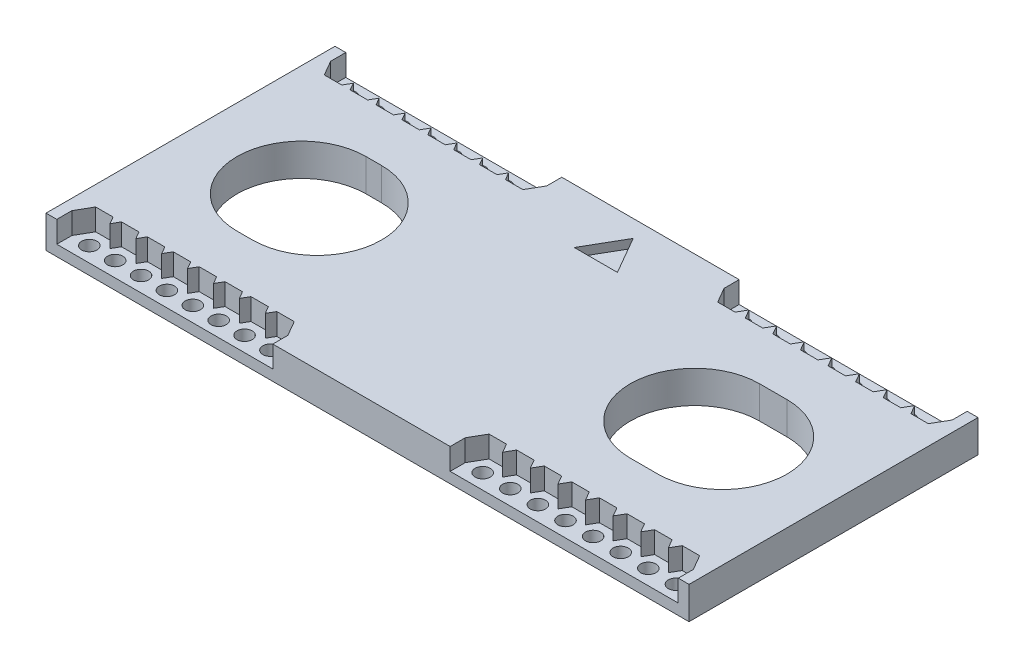
SolidWorks part; units mm, degrees
note: The reader was unsure of these and kept them because the rebuilt part matched: shared geometry of "Sketch1<5>".
ref_plane "Front Plane" through (0, 0, 0) normal (0, 0, 1) x (1, 0, 0)
ref_plane "Top Plane" through (0, 0, 0) normal (0, 1, 0) x (1, 0, 0)
ref_plane "Right Plane" through (0, 0, 0) normal (1, 0, 0) x (0, 0, -1)
sketch "Sketch1" plane through (0, 0, 0) normal (0, 1, 0) x (1, 0, 0)
  line L0 (0, 38.1) -> (0, -38.1) construction
  line L1 (156.464, 38.1) -> (164.592, -38.1) construction
  line L2 (-5.0555, 33.6582) -> (-3.81, 35.8155)
  line L3 (-5.0555, 33.6582) -> (178.2835, 33.6582)
  line L4 (-5.0555, 33.6582) -> (-5.0555, 0)
  line L5 (-5.0555, 0) -> (178.2835, 0)
  line L6 (178.2835, 33.6582) -> (178.2835, 0)
  line L7 (-3.81, 35.8155) -> (-2.5645, 33.6582)
  line L8 (0, 38.1) -> (-3.8467, 35.8791) construction
  line L9 (0, 38.1) -> (3.81, 38.1) construction
  line L10 (3.81, 38.1) -> (7.62, 38.1) construction
  line L11 (7.62, 38.1) -> (7.62, 33.6582) construction
  line L12 (0, 38.1) -> (-3.81, 38.1) construction
  line L13 (2.5645, 33.6582) -> (3.81, 35.8155)
  line L14 (3.81, 35.8155) -> (5.0555, 33.6582)
  line L15 (10.1845, 33.6582) -> (11.43, 35.8155)
  line L16 (11.43, 35.8155) -> (12.6755, 33.6582)
  line L17 (17.8045, 33.6582) -> (19.05, 35.8155)
  line L18 (19.05, 35.8155) -> (20.2955, 33.6582)
  line L19 (25.4245, 33.6582) -> (26.67, 35.8155)
  line L20 (26.67, 35.8155) -> (27.9155, 33.6582)
  line L21 (33.0445, 33.6582) -> (34.29, 35.8155)
  line L22 (34.29, 35.8155) -> (35.5355, 33.6582)
  line L23 (40.6645, 33.6582) -> (41.91, 35.8155)
  line L24 (41.91, 35.8155) -> (43.1555, 33.6582)
  line L25 (48.2845, 33.6582) -> (49.53, 35.8155)
  line L26 (49.53, 35.8155) -> (50.7755, 33.6582)
  line L27 (55.9045, 33.6582) -> (57.15, 35.8155)
  line L28 (57.15, 35.8155) -> (58.3955, 33.6582)
  line L29 (-3.81, 35.8155) -> (3.81, 35.8155) construction
  line L30 (7.62, 38.1) -> (15.24, 38.1) construction
  line L31 (178.2835, 33.6582) -> (176.784, 36.2554)
  line L32 (176.784, 36.2554) -> (175.2845, 33.6582)
  line L33 (172.72, 38.1) -> (176.5667, 35.8791) construction
  line L34 (172.72, 38.1) -> (176.784, 38.1) construction
  line L35 (172.72, 38.1) -> (168.656, 38.1) construction
  line L36 (168.656, 38.1) -> (164.592, 38.1) construction
  line L37 (170.1555, 33.6582) -> (168.656, 36.2554)
  line L38 (168.656, 36.2554) -> (167.1565, 33.6582)
  line L39 (162.0275, 33.6582) -> (160.528, 36.2554)
  line L40 (160.528, 36.2554) -> (159.0285, 33.6582)
  line L41 (153.8995, 33.6582) -> (152.4, 36.2554)
  line L42 (152.4, 36.2554) -> (150.9005, 33.6582)
  line L43 (145.7715, 33.6582) -> (144.272, 36.2554)
  line L44 (144.272, 36.2554) -> (142.7725, 33.6582)
  line L45 (137.6435, 33.6582) -> (136.144, 36.2554)
  line L46 (136.144, 36.2554) -> (134.6445, 33.6582)
  line L47 (129.5155, 33.6582) -> (128.016, 36.2554)
  line L48 (128.016, 36.2554) -> (126.5165, 33.6582)
  line L49 (121.3875, 33.6582) -> (119.888, 36.2554)
  line L50 (119.888, 36.2554) -> (118.3885, 33.6582)
  line L51 (113.2595, 33.6582) -> (111.76, 36.2554)
  line L52 (111.76, 36.2554) -> (110.2605, 33.6582)
  line L53 (-8.304, 42.5418) -> (181.024, 42.5418)
  line L54 (15.24, 42.5418) -> (15.24, 33.6582) construction
  line L55 (-5.129, 42.5418) -> (-5.129, 38.1)
  line L56 (-8.304, 42.5418) -> (-8.304, 0)
  line L58 (176.784, 36.2554) -> (177.849, 38.1)
  line L59 (177.849, 38.1) -> (177.849, 42.5418)
  line L60 (178.2835, 0) -> (181.024, 0)
  line L61 (-5.0555, 0) -> (-8.304, 0)
  line L62 (57.15, 35.8155) -> (58.469, 38.1)
  line L63 (58.469, 38.1) -> (58.469, 42.5418)
  line L64 (111.76, 36.2554) -> (110.695, 38.1)
  line L65 (110.695, 38.1) -> (110.695, 42.5418)
  line L66 (181.024, 42.5418) -> (181.024, 0)
  line L67 (-5.129, 38.1) -> (-3.8467, 35.8791)
  line L68 (-3.8467, 35.8791) -> (-3.81, 35.8155)
  circle A0 centre (0, 38.1) radius 2.2479
  circle A1 centre (0, -38.1) radius 2.2479 construction
  circle A2 centre (7.62, 38.1) radius 2.2479
  circle A3 centre (7.62, -38.1) radius 2.2479 construction
  circle A4 centre (15.24, 38.1) radius 2.2479
  circle A5 centre (15.24, -38.1) radius 2.2479 construction
  circle A6 centre (22.86, 38.1) radius 2.2479
  circle A7 centre (22.86, -38.1) radius 2.2479 construction
  circle A8 centre (30.48, 38.1) radius 2.2479
  circle A9 centre (30.48, -38.1) radius 2.2479 construction
  circle A10 centre (38.1, 38.1) radius 2.2479
  circle A11 centre (38.1, -38.1) radius 2.2479 construction
  circle A12 centre (45.72, 38.1) radius 2.2479
  circle A13 centre (45.72, -38.1) radius 2.2479 construction
  circle A14 centre (53.34, 38.1) radius 2.2479
  circle A15 centre (53.34, -38.1) radius 2.2479 construction
  circle A16 centre (115.824, 38.1) radius 2.2479
  circle A17 centre (115.824, -38.1) radius 2.2479 construction
  circle A18 centre (123.952, 38.1) radius 2.2479
  circle A19 centre (123.952, -38.1) radius 2.2479 construction
  circle A20 centre (132.08, 38.1) radius 2.2479
  circle A21 centre (132.08, -38.1) radius 2.2479 construction
  circle A22 centre (140.208, 38.1) radius 2.2479
  circle A23 centre (140.208, -38.1) radius 2.2479 construction
  circle A24 centre (148.336, 38.1) radius 2.2479
  circle A25 centre (148.336, -38.1) radius 2.2479 construction
  circle A26 centre (156.464, 38.1) radius 2.2479
  circle A27 centre (156.464, -38.1) radius 2.2479 construction
  circle A28 centre (164.592, 38.1) radius 2.2479
  circle A29 centre (164.592, -38.1) radius 2.2479 construction
  circle A30 centre (172.72, 38.1) radius 2.2479
  circle A31 centre (172.72, -38.1) radius 2.2479 construction
  circle A32 centre (15.24, 0) radius 19
  circle A34 centre (15.24, 0) radius 23.544
  point P4 (0, 0)
  point P79 (3.81, 38.1)
  dimension "D1" = 76.2
  dimension "D2" = 4.4958
  dimension "D5" = 8
  dimension "D8" = 38
  dimension "D15" = 3.175
  dimension "D4" = 7.62
  dimension "D6" = 8.128
  dimension "D7" = 117.348
  dimension "D9" = 4.4418
  dimension "D10" = 120
  dimension "D11" = 9
  dimension "D12" = 120
  dimension "D13" = 9
  dimension "D16" = 3.175
  dimension "D3" = 8
extrude "Boss-Extrude1" add sketch "Sketch1" against normal blind 9.525
extrude "Cut-Extrude1" cut sketch "Sketch1<5>" against normal blind 6.35
sketch "Sketch1<5>" plane through (0, 0, 0) normal (0, 1, 0) x (1, 0, 0) same geometry as "Sketch1"
mirror "Mirror1" about plane through (0, 0, 0) normal (0, 0, 1) of bodies 102
sketch "Sketch2" plane through (0, 0, 0) normal (0, 1, 0) x (1, 0, 0)
  line L0 (148.336, 0) -> (140.208, 0) construction
  line L1 (24.384, 0) -> (28.956, 0) construction
  line L3 (148.336, 0) -> (140.208, 0) construction
  line L4 (148.336, -19) -> (140.208, -19)
  line L5 (148.336, 19) -> (140.208, 19)
  line L6 (28.956, 0) -> (24.384, 0) construction
  line L7 (28.956, -19) -> (24.384, -19)
  line L8 (28.956, 19) -> (24.384, 19)
  arc A2 (148.336, -19) -> (148.336, 19) centre (148.336, 0) ccw
  arc A3 (140.208, 19) -> (140.208, -19) centre (140.208, 0) ccw
  arc A4 (28.956, -19) -> (28.956, 19) centre (28.956, 0) ccw
  arc A5 (24.384, 19) -> (24.384, -19) centre (24.384, 0) ccw
  circle A6 centre (15.24, 0) radius 19 construction
  point P5 (115.824, 38.1)
  point P6 (172.72, 38.1)
  point P8 (53.34, 38.1)
  point P9 (0, 38.1)
  point P12 (144.272, 0)
  point P21 (26.67, 0)
  dimension "D1" = 24.384
  dimension "D2" = 24.384
  dimension "D3" = 24.384
  dimension "D4" = 24.384
extrude "Cut-Extrude2" cut sketch "Sketch2" against normal through all
sketch "Sketch4" plane through (0, 0, 0) normal (0, 1, 0) x (1, 0, 0)
  line L0 (78.232, 26.4633) -> (84.582, 37.4618)
  line L1 (84.582, 37.4618) -> (90.932, 26.4633)
  line L2 (90.932, 26.4633) -> (78.232, 26.4633)
  line L3 (58.469, 42.5418) -> (110.695, 42.5418) construction
  point P3 (84.582, 42.5418)
  dimension "D1" = 12.7
  dimension "D2" = 5.08
extrude "Cut-Extrude3" cut sketch "Sketch4" against normal blind 2.54
